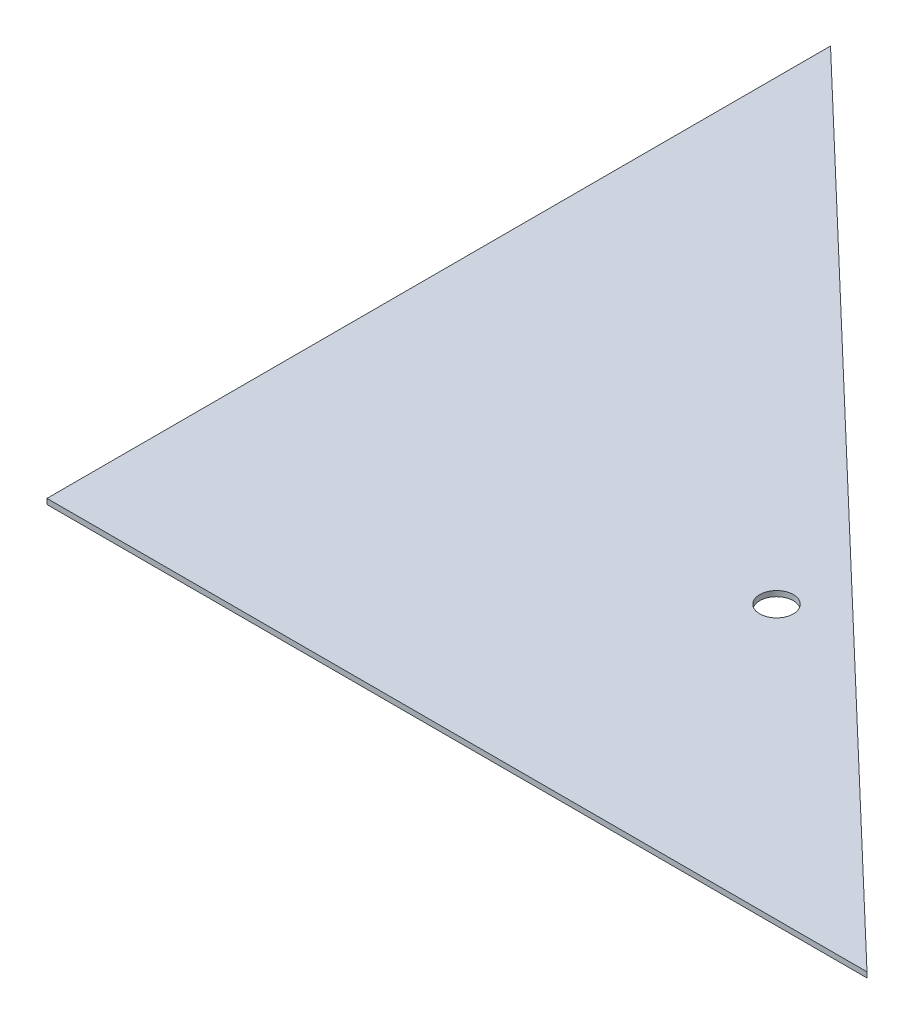
SolidWorks part; units mm, degrees
ref_plane "Front Plane" through (0, 0, 0) normal (0, 0, 1) x (1, 0, 0)
ref_plane "Top Plane" through (0, 0, 0) normal (0, 1, 0) x (1, 0, 0)
ref_plane "Right Plane" through (0, 0, 0) normal (1, 0, 0) x (0, 0, -1)
sketch "Sketch1" plane through (0, 0, 0) normal (0, 1, 0) x (1, 0, 0)
  line L0 (-218.5319, 50.0359) -> (-218.5319, -320.5617)
  line L1 (-218.5319, -320.5617) -> (169.3261, -320.5617)
  line L2 (169.3261, -320.5617) -> (-218.5319, 50.0359)
  dimension "D1" = 387.858
  dimension "D2" = 370.5977
extrude "Boss-Extrude1" add sketch "Sketch1" along normal blind 2.54
sketch "Sketch2" plane through (0, 2.54, 0) normal (0, 1, 0) x (1, 0, 0)
  line L0 (-218.5319, 50.0359) -> (-218.5319, -320.5617) construction
  line L1 (169.3261, -320.5617) -> (-218.5319, 50.0359) construction
  circle A0 centre (-2.6319, -191.387) radius 7.9375
  dimension "D1" = 215.9
  dimension "D2" = 15.875
  dimension "D3" = 25.4
extrude "Cut-Extrude1" cut sketch "Sketch2" against normal blind 2.54
